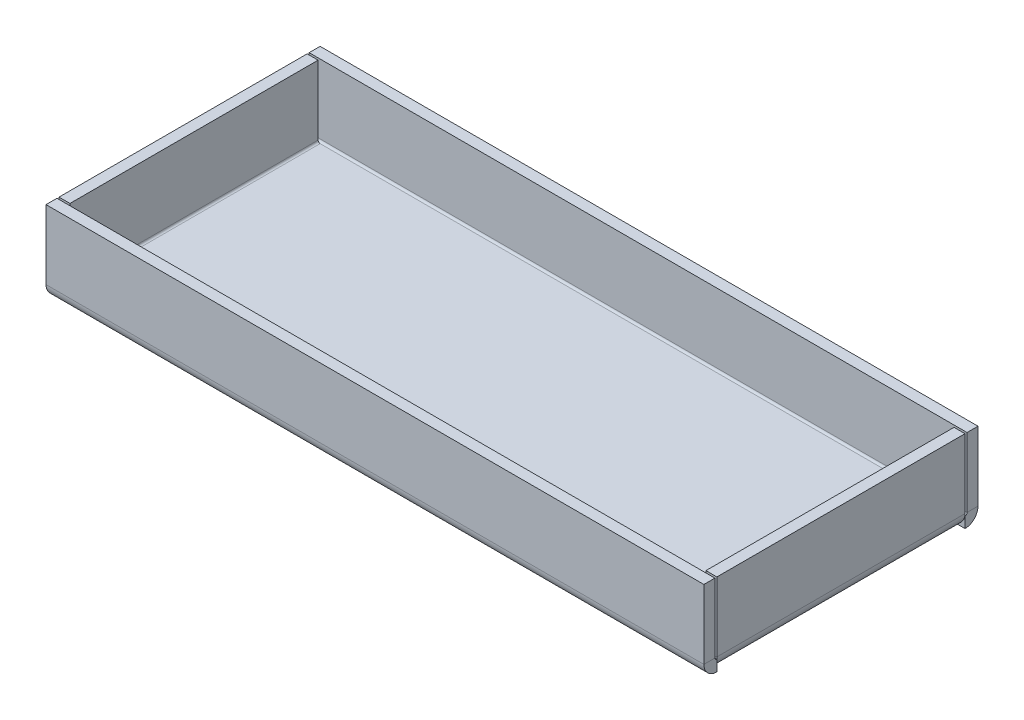
SolidWorks part; units mm, degrees
note: The reader was unsure of these and kept them because the rebuilt part matched: flange length of "Brida de arista1", "Brida de arista2".
ref_plane "Front" through (0, 0, 0) normal (0, 0, 1) x (1, 0, 0)
ref_plane "Top" through (0, 0, 0) normal (0, 1, 0) x (1, 0, 0)
ref_plane "Right" through (0, 0, 0) normal (1, 0, 0) x (0, 0, -1)
sketch "Croquis2" plane through (0, 0, 0) normal (0, 1, 0) x (1, 0, 0)
  line L1 (0, 0) -> (240, 0)
  line L2 (0, 0) -> (0, 100)
  line L3 (0, 100) -> (240, 100)
  line L4 (240, 0) -> (240, 100)
  dimension "D1" = 100
  dimension "D2" = 240
base flange "Brida base1" sketch "Croquis2" thickness 4 reverse thickness direction yes parameters "D1"=0.7366
edge flange "Brida de arista1" sketch "Croquis11" flange profiles "Croquis11", "Croquis12" flange angle 90 flange length 30 flange position material inside bend radius 0.7366 thickness 4 relief rectangular parameters "D6"=10, "D8"=0
sketch "Croquis11" plane through (0, 4, 0) normal (0, 0, -1) x (-1, 0, 0)
  line L2 (-240, 0) -> (-240, 26)
  line L3 (-240, 26) -> (0, 26)
  line L4 (0, 26) -> (0, 0)
  line L13 (0, 0) -> (-240, 0) construction
  line L14 (0, 0) -> (-240, 0)
sketch "Croquis12" plane through (0, 4, -100) normal (0, 0, 1) x (1, 0, 0)
  line L2 (0, 0) -> (0, 26)
  line L3 (0, 26) -> (240, 26)
  line L4 (240, 26) -> (240, 0)
  line L9 (240, 0) -> (0, 0) construction
  line L10 (240, 0) -> (0, 0)
bend "Pliegue de arista1" bend radius 0.7366 bend angle 90 parameters "D5"=1
bend "Pliegue de arista2" bend radius 0.7366 bend angle 90 parameters "D5"=2
edge flange "Brida de arista2" sketch "Croquis18" flange profiles "Croquis18", "Croquis19" flange angle 90 flange length 30 flange position material inside bend radius 0.7366 thickness 4 relief none parameters "D6"=10, "D8"=0
sketch "Croquis18" plane through (240, 4, 0) normal (-1, 0, 0) x (0, 0, 1)
  line L2 (-95.2634, 0) -> (-95.2634, 26)
  line L3 (-95.2634, 26) -> (-4.7366, 26)
  line L4 (-4.7366, 26) -> (-4.7366, 0)
  line L25 (-4.7366, 0) -> (-95.2634, 0) construction
  line L26 (-4.7366, 0) -> (-95.2634, 0)
sketch "Croquis19" plane through (0, 4, 0) normal (1, 0, 0) x (0, 0, -1)
  line L2 (4.7366, 0) -> (4.7366, 26)
  line L3 (4.7366, 26) -> (95.2634, 26)
  line L4 (95.2634, 26) -> (95.2634, 0)
  line L21 (95.2634, 0) -> (4.7366, 0) construction
  line L22 (95.2634, 0) -> (4.7366, 0)
bend "Pliegue de arista3" bend radius 0.7366 bend angle 90 parameters "D5"=3
bend "Pliegue de arista4" bend radius 0.7366 bend angle 90 parameters "D5"=4
sketch "Líneas de pliegue1" [suppressed] plane through (0, 0, 0) normal (0, 1, 0) x (1, 0, 0)
sketch "Cuadro delimitador1" [suppressed] plane through (0, 0, 0) normal (0, 1, 0) x (1, 0, 0)
sheet metal parameters "Chapa metálica1" thickness 4 parameters "D1"=0.7366
flat pattern "Chapa desplegada1" [suppressed]
sketch "Líneas de pliegue2" plane through (0, 0, 0) normal (0, 1, 0) x (1, 0, 0)
sketch3d "Cuadro delimitador2" [suppressed]
  line L0 (-240, 100, 0) -> (0, 100, 0) construction
  line L1 (-240, 0, 0) -> (0, 0, 0) construction
  line L2 (-240, 100, 0) -> (-240, 0, 0) construction
  line L3 (0, 100, 0) -> (0, 0, 0) construction
sheet metal parameters "Chapa metálica2" thickness 4 parameters "D1"=0.7366
flat pattern "Chapa desplegada1"
sketch "Líneas de pliegue2" plane through (0, 0, 0) normal (0, -1, 0) x (-1, 0, 0)
  line L0 (0, 97.4127) -> (-240, 97.4127) construction
  line L1 (-240, 2.5873) -> (0, 2.5873) construction
  line L2 (0, 97.4127) -> (-240, 97.4127) construction
  line L3 (-240, 2.5873) -> (0, 2.5873) construction
sketch3d "Cuadro delimitador2" [suppressed]
  line L0 (-240, 124.8254, 0) -> (0, 124.8254, 0) construction
  line L1 (-240, -24.8254, 0) -> (0, -24.8254, 0) construction
  line L2 (-240, 124.8254, 0) -> (-240, -24.8254, 0) construction
  line L3 (0, 124.8254, 0) -> (0, -24.8254, 0) construction
bend of the flat pattern "Aplanar-<Pliegue de arista1>1"
bend of the flat pattern "Aplanar-<Pliegue de arista2>1"
sheet metal parameters "Chapa metálica3" thickness 4 parameters "D1"=0.7366
flat pattern "Chapa desplegada1"
sketch "Líneas de pliegue2" plane through (0, 0, 0) normal (0, -1, 0) x (-1, 0, 0)
  line L0 (0, 97.4127) -> (-240, 97.4127) construction
  line L1 (-240, 2.5873) -> (0, 2.5873) construction
  line L2 (0, 97.4127) -> (-240, 97.4127) construction
  line L3 (-240, 2.5873) -> (0, 2.5873) construction
  line L4 (-2.5873, 4.7366) -> (-2.5873, 95.2634) construction
  line L5 (-237.4127, 95.2634) -> (-237.4127, 4.7366) construction
  line L6 (-2.5873, 4.7366) -> (-2.5873, 95.2634) construction
  line L7 (-237.4127, 95.2634) -> (-237.4127, 4.7366) construction
sketch3d "Cuadro delimitador2" [suppressed]
  line L0 (-264.8254, 124.8254, 0) -> (24.8254, 124.8254, 0) construction
  line L1 (-264.8254, -24.8254, 0) -> (24.8254, -24.8254, 0) construction
  line L2 (-264.8254, 124.8254, 0) -> (-264.8254, -24.8254, 0) construction
  line L3 (24.8254, 124.8254, 0) -> (24.8254, -24.8254, 0) construction
bend of the flat pattern "Aplanar-<Pliegue de arista1>1"
bend of the flat pattern "Aplanar-<Pliegue de arista2>1"
bend of the flat pattern "Aplanar-<Pliegue de arista3>1"
bend of the flat pattern "Aplanar-<Pliegue de arista4>1"
